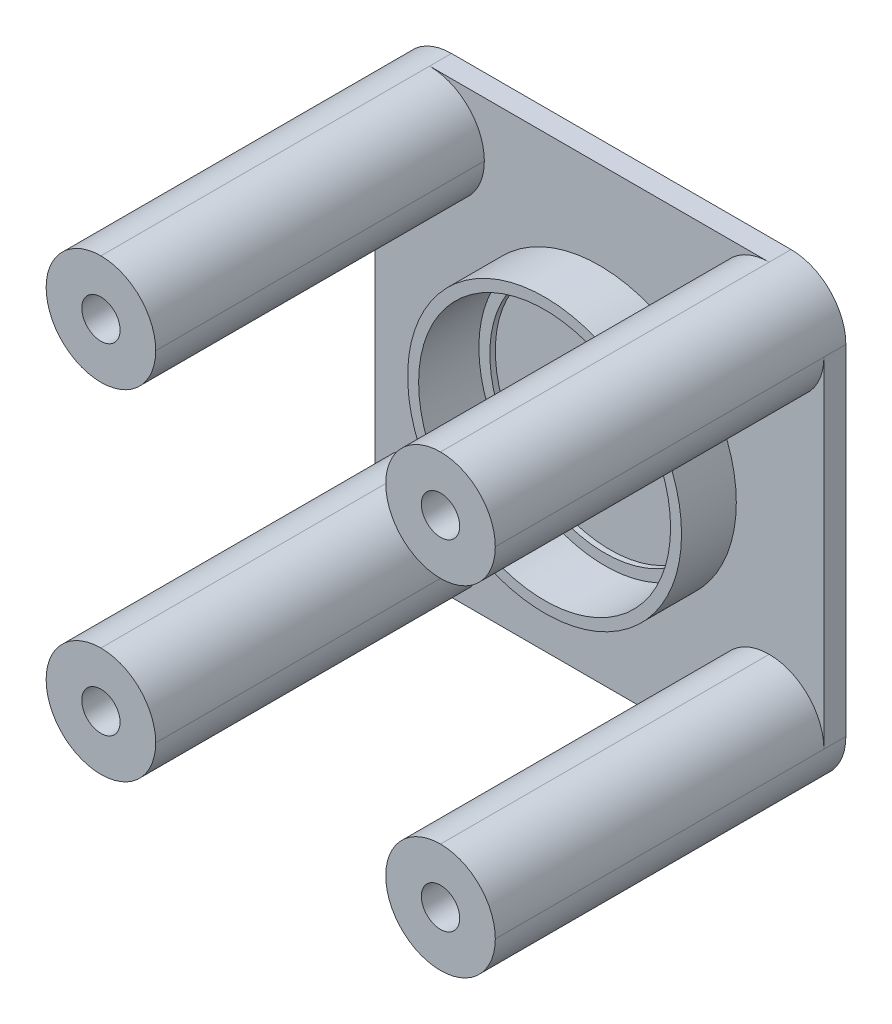
SolidWorks part; units mm, degrees
ref_plane "Front Plane" through (0, 0, 0) normal (0, 0, 1) x (1, 0, 0)
ref_plane "Top Plane" through (0, 0, 0) normal (0, 1, 0) x (1, 0, 0)
ref_plane "Right Plane" through (0, 0, 0) normal (1, 0, 0) x (0, 0, -1)
sketch "Sketch1" plane through (0, 0, 0) normal (0, 0, 1) x (1, 0, 0)
  line L0 (-55.0083, 19.8562) -> (-14.0083, 19.8562) construction
  line L1 (-55.0083, 24.8562) -> (-14.0083, 24.8562)
  line L2 (-55.0083, 24.8562) -> (-55.0083, -16.1438)
  line L3 (-55.0083, -16.1438) -> (-14.0083, -16.1438)
  line L4 (-14.0083, 24.8562) -> (-14.0083, -16.1438)
  line L5 (-50.0083, 24.8562) -> (-50.0083, -16.1438) construction
  line L6 (-55.0083, -11.1438) -> (-14.0083, -11.1438) construction
  line L7 (-19.0083, 24.8562) -> (-19.0083, -16.1438) construction
  line L8 (-55.0083, 24.8562) -> (-14.0083, -16.1438) construction
  line L9 (-55.0083, -16.1438) -> (-14.0083, 24.8562) construction
  circle A0 centre (-50.0083, 19.8562) radius 1.75
  circle A1 centre (-50.0083, -11.1438) radius 1.75
  circle A2 centre (-19.0083, -11.1438) radius 1.75
  circle A3 centre (-19.0083, 19.8562) radius 1.75
  circle A4 centre (-34.5083, 4.3562) radius 1.25
  dimension "D1" = 41
  dimension "D2" = 41
  dimension "D3" = 5
  dimension "D4" = 5
  dimension "D5" = 5
  dimension "D6" = 5
extrude "Boss-Extrude1" add sketch "Sketch1" along normal blind 2
sketch "Sketch2" plane through (0, 0, 2) normal (0, 0, 1) x (1, 0, 0)
  line L1 (-55.0083, 24.8562) -> (-45.0083, 24.8562)
  line L2 (-55.0083, 24.8562) -> (-55.0083, 14.8562)
  line L3 (-55.0083, 14.8562) -> (-45.0083, 14.8562)
  line L4 (-45.0083, 24.8562) -> (-45.0083, 14.8562)
  line L5 (-55.0083, -16.1438) -> (-45.0083, -16.1438)
  line L6 (-55.0083, -16.1438) -> (-55.0083, -6.1438)
  line L7 (-55.0083, -6.1438) -> (-45.0083, -6.1438)
  line L8 (-45.0083, -16.1438) -> (-45.0083, -6.1438)
  line L9 (-14.0083, -16.1438) -> (-24.0083, -16.1438)
  line L10 (-14.0083, -16.1438) -> (-14.0083, -6.1438)
  line L11 (-14.0083, -6.1438) -> (-24.0083, -6.1438)
  line L12 (-24.0083, -16.1438) -> (-24.0083, -6.1438)
  line L13 (-14.0083, 24.8562) -> (-24.0083, 24.8562)
  line L14 (-14.0083, 24.8562) -> (-14.0083, 14.8562)
  line L15 (-14.0083, 14.8562) -> (-24.0083, 14.8562)
  line L16 (-24.0083, 24.8562) -> (-24.0083, 14.8562)
  circle A0 centre (-50.0083, 19.8562) radius 1.75
  circle A1 centre (-50.0083, -11.1438) radius 1.75
  circle A2 centre (-19.0083, -11.1438) radius 1.75
  circle A3 centre (-19.0083, 19.8562) radius 1.75
  dimension "D1" = 10
  dimension "D2" = 10
  dimension "D3" = 10
  dimension "D4" = 10
  dimension "D5" = 10
  dimension "D6" = 10
  dimension "D7" = 10
  dimension "D8" = 10
extrude "Boss-Extrude2" add sketch "Sketch2" along normal blind 30
fillet "Fillet1" radius 5 16 edges at (-24.0083, 24.8562, 17) (-24.0083, -6.1438, 17) (-55.0083, -6.1438, 17) (-55.0083, 14.8562, 17) (-45.0083, 24.8562, 17) (-45.0083, -6.1438, 17) (-45.0083, -16.1438, 17) (-24.0083, -16.1438, 17) (-14.0083, -6.1438, 17) (-14.0083, 14.8562, 17) (-24.0083, 14.8562, 17) (-45.0083, 14.8562, 17) (-14.0083, -16.1438, 16) (-14.0083, 24.8562, 16) (-55.0083, -16.1438, 16) (-55.0083, 24.8562, 16)
sketch "Sketch3" plane through (0, 0, 2) normal (0, 0, 1) x (1, 0, 0)
  circle A1 centre (-34.5083, 4.3562) radius 10.5
extrude "Cut-Extrude1" cut sketch "Sketch3" against normal blind 1
sketch "Sketch4" plane through (0, 0, 2) normal (0, 0, 1) x (1, 0, 0)
  circle A0 centre (-34.5083, 4.3562) radius 11.5
extrude "Cut-Extrude2" cut sketch "Sketch4" against normal blind 0.5
sketch "Sketch6" plane through (0, 0, 2) normal (0, 0, 1) x (1, 0, 0)
  line L0 (-26.47, -3.8678) -> (-34.5083, 4.3562) construction
  circle A0 centre (-44.9502, -0.4246) radius 0.0157
  circle A1 centre (-34.5083, 4.3562) radius 11.5 construction
  circle A2 centre (-34.5083, 4.3562) radius 12.5
  circle A3 centre (-34.5083, 4.3562) radius 11.5
  circle M1 centre (-34.5083, 4.3562) radius 11.5
extrude "Boss-Extrude3" add sketch "Sketch6" along normal blind 5 contours A2 A3 M1 region at (-46.6548, 4.3562, 2)
